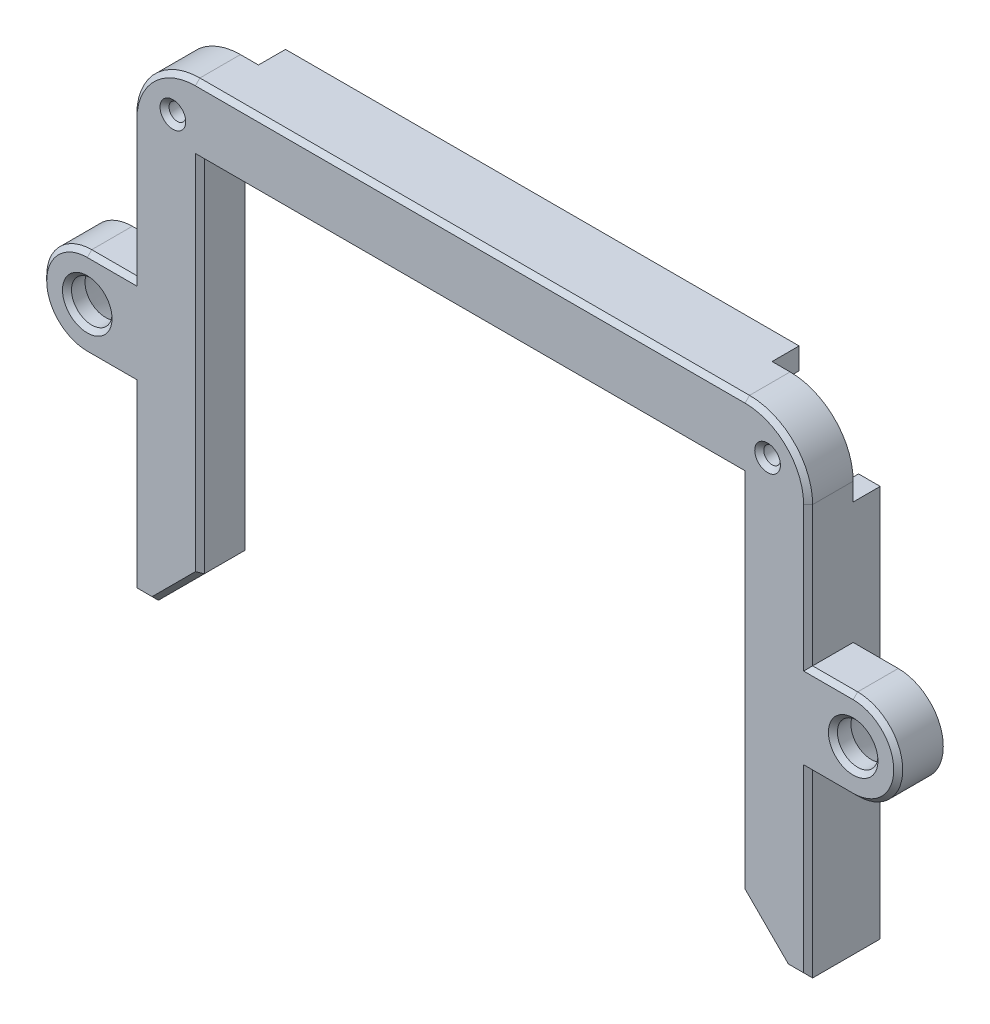
SolidWorks part; units mm, degrees
ref_plane "Front Plane" through (0, 0, 0) normal (0, 0, 1) x (1, 0, 0)
ref_plane "Top Plane" through (0, 0, 0) normal (0, 1, 0) x (1, 0, 0)
ref_plane "Right Plane" through (0, 0, 0) normal (1, 0, 0) x (0, 0, -1)
sketch "Sketch1" plane through (0, 0, 0) normal (0, 0, 1) x (1, 0, 0)
  line L0 (-30, -25) -> (-30, 20)
  line L1 (-35, -25) -> (35, -25) construction
  line L2 (-35, -25) -> (-35, 25) construction
  line L3 (-35, 25) -> (35, 25) construction
  line L4 (35, -25) -> (35, 25) construction
  line L5 (-30, 20) -> (30, 20)
  line L6 (30, 20) -> (30, -25)
  line L7 (-30, -25) -> (-37.5, -25)
  line L8 (-37.5, -25) -> (-37.5, 27.5)
  line L9 (-37.5, 27.5) -> (37.5, 27.5)
  line L10 (37.5, 27.5) -> (37.5, -25)
  line L11 (37.5, -25) -> (30, -25)
  circle A0 centre (-33, 23) radius 0.925
  circle A1 centre (33, 23) radius 0.925
  point P4 (0, 25)
  point P5 (-35, 0)
  dimension "D6" = 1.85
  dimension "D1" = 70
  dimension "D2" = 50
  dimension "D3" = 5
  dimension "D4" = 5
  dimension "D5" = 5
  dimension "D7" = 2
  dimension "D8" = 2
  dimension "D9" = 2
  dimension "D10" = 2
  dimension "D11" = 7.5
  dimension "D12" = 7.5
  dimension "D13" = 7.5
extrude "Boss-Extrude1" add sketch "Sketch1" along normal blind 5
sketch "Sketch2" plane through (0, 0, 0) normal (0, 0, 1) x (1, 0, 0)
  line L0 (37.5, -25) -> (30, -25) construction
  line L1 (37.5, 27.5) -> (30, 27.5)
  line L2 (37.5, 27.5) -> (37.5, -25)
  line L3 (37.5, -25) -> (35.1, -25)
  line L4 (35.1, 25.1) -> (35.1, -25)
  line L5 (-37.5, 27.5) -> (-30, 27.5)
  line L6 (-37.5, 27.5) -> (-37.5, -25)
  line L7 (-37.5, -25) -> (-35.1, -25)
  line L8 (-35.1, 25.1) -> (-35.1, -25)
  line L9 (30, 27.5) -> (-30, 27.5)
  line L11 (35.1, 25.1) -> (-35.1, 25.1)
  line L12 (35, -25) -> (35, 25) construction
  line L15 (-35, -25) -> (-35, 25) construction
  line L16 (-35, 25) -> (35, 25) construction
  line L17 (-37.5, -25) -> (-30, -25) construction
  dimension "D1" = 0.1
  dimension "D2" = 0.1
  dimension "D3" = 0.1
extrude "Boss-Extrude2" add sketch "Sketch2" against normal blind 3
sketch "Sketch7" plane through (0, 0, 0) normal (0, 0, -1) x (-1, 0, 0)
  line L1 (-28.5, 18.5) -> (-37.5, 18.5)
  line L2 (-28.5, 18.5) -> (-28.5, 27.5)
  line L3 (-28.5, 27.5) -> (-37.5, 27.5)
  line L4 (-37.5, 18.5) -> (-37.5, 27.5)
  line L5 (-28.5, 18.5) -> (-37.5, 27.5) construction
  line L6 (-28.5, 27.5) -> (-37.5, 18.5) construction
  line L7 (28.5, 18.5) -> (37.5, 18.5)
  line L8 (28.5, 18.5) -> (28.5, 27.5)
  line L9 (28.5, 27.5) -> (37.5, 27.5)
  line L10 (37.5, 18.5) -> (37.5, 27.5)
  line L11 (28.5, 18.5) -> (37.5, 27.5) construction
  line L12 (28.5, 27.5) -> (37.5, 18.5) construction
  point P0 (-33, 23)
  point P5 (33, 23)
extrude "Cut-Extrude3" cut sketch "Sketch7" along normal through all
sketch "Sketch3" plane through (0, 0, 0) normal (0, 0, 1) x (1, 0, 0)
  line L0 (37.5, 27.5) -> (37.5, -25) construction
  line L1 (42.5, 5) -> (37.5, 5)
  line L3 (42.5, -5) -> (37.5, -5)
  line L4 (37.5, 5) -> (37.5, -5)
  line L5 (-37.5, -25) -> (-37.5, 27.5) construction
  line L6 (-42.5, 5) -> (-37.5, 5)
  line L8 (-42.5, -5) -> (-37.5, -5)
  line L9 (-37.5, 5) -> (-37.5, -5)
  arc A0 (42.5, -5) -> (42.5, 5) centre (42.5, 0) ccw
  arc A1 (-42.5, 5) -> (-42.5, -5) centre (-42.5, 0) ccw
  circle A2 centre (42.5, 0) radius 2.25
  circle A3 centre (-42.5, 0) radius 2.25
  dimension "D1" = 10
  dimension "D2" = 10
  dimension "D3" = 4.5
  dimension "D4" = 4.5
extrude "Boss-Extrude3" add sketch "Sketch3" along normal up to surface (5 mm away) up to face at (0, -0.625, 5)
sketch "Sketch4" plane through (0, 0, 0) normal (0, 0, -1) x (-1, 0, 0)
  circle A0 centre (-42.5, 0) radius 3.5
  circle A1 centre (42.5, 0) radius 3.5
  dimension "D1" = 7
  dimension "D2" = 7
extrude "Cut-Extrude1" cut sketch "Sketch4" against normal blind 3
chamfer "Chamfer2" distance 5.1 angle 45 2 edges at (-30, -25, 2.5) (30, -25, 2.5)
fillet "Fillet1" radius 7 2 edges at (-37.5, 27.5, 2.5) (37.5, 27.5, 2.5)
chamfer "Chamfer3" distance 0.5 angle 45 26 edges at (-44.75, 0, 5) (40.25, 0, 5) (33.925, 23, 5) (-32.075, 23, 5) (-37.5, -15, 5) (-40, -5, 5) (-47.5, 0, 5) (-40, 5, 5) (-37.5, 12.75, 5) (0, 27.5, 5) (37.5, 12.75, 5) (40, 5, 5) (47.5, 0, 5) (40, -5, 5) (37.5, -15, 5) (36.3, -25, 5) (32.55, -22.45, 5) (30, 0.05, 5) (0, 20, 5) (-30, 0.05, 5) (-32.55, -22.45, 5) (-36.3, -25, 5) (-32.075, 23, 0) (33.925, 23, 0) (35.4497, 25.4497, 5) (-35.4497, 25.4497, 5)
chamfer "Chamfer1" distance 2.5 distance2 1.25 2 edges at (-46, 0, 3) (39, 0, 3) first distance on face at (-46, 0, 3) first distance on face at (39, 0, 3)
